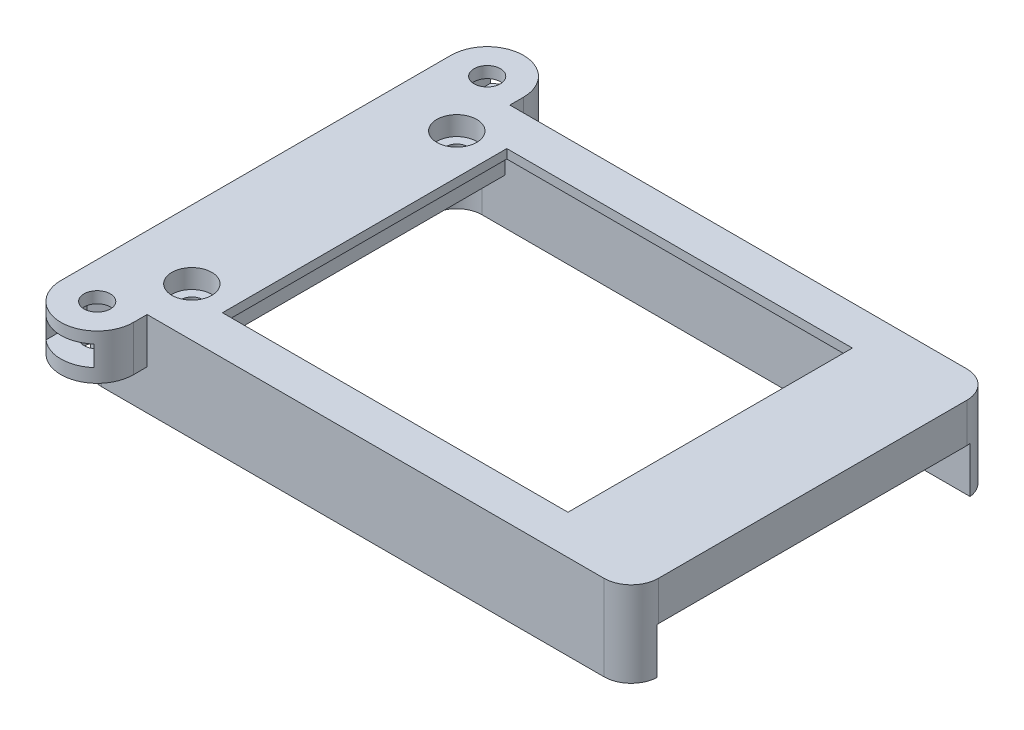
SolidWorks part; units mm, degrees
ref_plane "Front Plane" through (0, 0, 0) normal (0, 0, 1) x (1, 0, 0)
ref_plane "Top Plane" through (0, 0, 0) normal (0, 1, 0) x (1, 0, 0)
ref_plane "Right Plane" through (0, 0, 0) normal (1, 0, 0) x (0, 0, -1)
sketch "Sketch1" plane through (0, 0, 0) normal (0, 0, 1) x (1, 0, 0)
  line L0 (-23.495, -2.8321) -> (-20.447, -2.8321) construction
  line L1 (-20.447, 0) -> (-20.447, -2.8321) construction
  line L2 (-23.495, -2.8321) -> (-26.035, -2.8321) construction
  line L3 (-26.035, -2.8321) -> (-26.035, -4.4196) construction
  line L4 (-23.495, -2.8321) -> (-20.447, -2.8321) construction
  line L5 (-20.447, 0) -> (-20.447, -2.8321) construction
  line L6 (-23.495, -2.8321) -> (-26.035, -2.8321) construction
  line L7 (-26.035, -2.8321) -> (-26.035, -4.4196) construction
  line L8 (-9.4742, -6.2992) -> (-26.035, -6.2992) construction
  line L9 (-26.035, -6.2992) -> (-26.035, -4.4196) construction
  line L10 (-9.4742, -6.2992) -> (-26.035, -6.2992) construction
  line L11 (-26.035, -6.2992) -> (-26.035, -4.4196) construction
  line L12 (-20.947, 1.5) -> (-20.947, -2.8321)
  line L13 (-20.947, -2.8321) -> (-26.035, -2.8321)
  line L14 (-26.035, -2.8321) -> (-26.035, -7.9085)
  line L15 (-28.6272, -8.4085) -> (-21.9464, -8.4085) construction
  line L16 (-28.6272, -8.4085) -> (-21.9464, -8.4085) construction
  line L17 (-26.035, -7.9085) -> (-31.035, -7.9085)
  line L18 (-31.035, -7.9085) -> (-31.035, 1.5)
  line L19 (-31.035, 1.5) -> (-20.947, 1.5)
  line L20 (-20.447, 0) -> (26.0604, 0) construction
  line L21 (-20.447, 0) -> (26.0604, 0) construction
  point P14 (-29.7744, 1.574)
  dimension "D1" = 1
  dimension "D2" = 0.5
  dimension "D3" = 1.5
  dimension "D4" = 5
extrude "Boss-Extrude1" add sketch "Sketch1" along normal mid plane 40
sketch "Sketch2" plane through (0, 1.5, 0) normal (0, 1, 0) x (1, 0, 0)
  line L0 (-24.6493, -17.145) -> (-20.947, -17.145)
  line L1 (-20.947, -20) -> (-20.947, 20) construction
  line L2 (-20.947, -17.145) -> (-20.947, -20)
  line L3 (-20.947, -20) -> (-26.035, -20)
  line L4 (-20.947, -20) -> (-31.035, -20) construction
  line L5 (-26.035, -20) -> (-26.035, -17.145)
  line L6 (-26.035, -20) -> (-26.035, 20) construction
  line L7 (-26.035, -17.145) -> (-26.035, -15.7593)
  line L8 (-23.495, 17.395) -> (-23.495, 20)
  line L9 (-20.947, 20) -> (-31.035, 20) construction
  line L10 (-23.495, 20) -> (-26.035, 20)
  line L11 (-26.035, 20) -> (-26.035, 15.7593)
  arc A0 (-26.035, -14.605) -> (-23.495, -17.145) centre (-23.495, -14.605) ccw construction
  arc A1 (-26.035, -14.605) -> (-23.495, -17.145) centre (-23.495, -14.605) ccw construction
  arc A2 (-23.495, 17.145) -> (-26.035, 14.605) centre (-23.495, 14.605) ccw construction
  arc A3 (-23.495, 17.145) -> (-26.035, 14.605) centre (-23.495, 14.605) ccw construction
  arc A4 (-26.035, -15.7593) -> (-24.6493, -17.145) centre (-23.495, -14.605) ccw
  arc A5 (-26.285, -14.605) -> (-23.495, -17.395) centre (-23.495, -14.605) ccw construction
  arc A6 (-23.495, 17.395) -> (-26.035, 15.7593) centre (-23.495, 14.605) ccw
  arc A7 (-23.495, 17.395) -> (-26.285, 14.605) centre (-23.495, 14.605) ccw construction
  point P27 (-26.035, 13.7261)
  dimension "D1" = 0.25
  dimension "D2" = 0.25
extrude "Boss-Extrude2" add sketch "Sketch2" against normal up to surface (9.4085 mm away) up to face at (-28.535, -7.9085, 0)
fillet "Fillet1" radius 3 2 edges at (-31.035, -3.2043, -20) (-31.035, -3.2043, 20)
sketch "Sketch5" plane through (0, 1.5, 0) normal (0, 1, 0) x (1, 0, 0)
  line L0 (-20.947, 20) -> (27.345, 20)
  line L1 (-20.947, -20) -> (27.345, -20)
  line L2 (30.345, -17) -> (30.345, 17)
  line L3 (-20.947, -20) -> (-20.947, 20) construction
  line L4 (-20.947, -20) -> (-20.947, 20)
  line L5 (29.845, -14.605) -> (29.845, 14.605) construction
  line L8 (19.05, 15.6781) -> (19.05, -15.6781) construction
  line L9 (19.05, -15.6781) -> (-19.05, -15.6781) construction
  line L10 (19.05, 15.6781) -> (-19.05, 15.6781) construction
  line L11 (-19.05, 15.6781) -> (-19.05, -15.6781) construction
  line L12 (19.05, 15.6781) -> (19.05, -15.6781)
  line L13 (19.05, -15.6781) -> (-19.05, -15.6781)
  line L14 (19.05, 15.6781) -> (-19.05, 15.6781)
  line L15 (-19.05, 15.6781) -> (-19.05, -15.6781)
  arc A0 (27.345, -20) -> (30.345, -17) centre (27.345, -17) ccw
  arc A1 (30.345, 17) -> (27.345, 20) centre (27.345, 17) ccw
  arc A2 (-31.035, -17) -> (-28.035, -20) centre (-28.035, -17) ccw construction
  dimension "D1" = 0.5
extrude "Boss-Extrude5" add sketch "Sketch5" against normal offset from surface (1 mm away) 0.5
sketch "Sketch6" plane through (0, 0.5, 0) normal (0, -1, 0) x (1, 0, 0)
  line L0 (-23.495, 17.145) -> (27.305, 17.145) construction
  line L1 (-20.947, 17.145) -> (26.1854, 17.145)
  line L2 (26.0604, -17.145) -> (-20.447, -17.145) construction
  line L3 (-20.947, 20) -> (-20.947, -20) construction
  line L4 (-20.947, 20) -> (-20.947, 17.145)
  line L5 (27.345, 20) -> (-20.947, 20) construction
  line L6 (27.345, 20) -> (-20.947, 20)
  line L7 (-20.947, -20) -> (27.345, -20) construction
  line L8 (30.345, -17) -> (30.345, 17) construction
  line L9 (-20.947, -20) -> (27.345, -20)
  line L10 (30.345, -17) -> (30.345, 17)
  line L11 (26.0604, 17.145) -> (26.0604, 14.4018) construction
  line L12 (26.0604, 17.145) -> (26.0604, 14.4018) construction
  line L13 (26.1854, 17.145) -> (26.1854, -17.395)
  line L14 (26.0604, -17.145) -> (-20.447, -17.145) construction
  line L15 (-20.947, -20) -> (-20.947, -17.395)
  line L16 (-20.947, -17.395) -> (26.1854, -17.395)
  arc A4 (30.345, 17) -> (27.345, 20) centre (27.345, 17) ccw construction
  arc A5 (30.345, 17) -> (27.345, 20) centre (27.345, 17) ccw
  arc A6 (27.345, -20) -> (30.345, -17) centre (27.345, -17) ccw construction
  arc A7 (27.345, -20) -> (30.345, -17) centre (27.345, -17) ccw
  dimension "D2" = 0.25
  dimension "D1" = 0.25
extrude "Boss-Extrude6" add sketch "Sketch6" along normal up to surface (3.3321 mm away)
sketch "Sketch7" plane through (0, -2.8321, 0) normal (0, -1, 0) x (1, 0, 0)
  line L1 (-20.947, 20) -> (27.345, 20)
  line L2 (-20.947, 20) -> (-20.947, 17.145)
  line L3 (-20.947, 17.145) -> (30.3415, 17.145)
  line L6 (-23.495, -20) -> (27.345, -20)
  line L7 (-23.495, -20) -> (-23.495, -17.395)
  line L8 (-23.495, -17.395) -> (30.3189, -17.395)
  arc A0 (30.345, 17) -> (27.345, 20) centre (27.345, 17) ccw construction
  arc A1 (27.345, -20) -> (30.345, -17) centre (27.345, -17) ccw construction
  arc A2 (30.3415, 17.145) -> (27.345, 20) centre (27.345, 17) ccw
  arc A3 (27.345, -20) -> (30.3189, -17.395) centre (27.345, -17) ccw
  point P12 (0, 0)
extrude "Boss-Extrude7" add sketch "Sketch7" along normal up to surface (5.0764 mm away) up to face at (-25.9411, -7.9085, 1.5134)
sketch "Sketch9" plane through (0, 1.5, 0) normal (0, 1, 0) x (1, 0, 0)
  line L0 (-31.035, 17) -> (-31.035, 21.5)
  line L1 (-23.035, 21.5) -> (-23.035, 20)
  line L2 (27.345, 20) -> (-28.035, 20) construction
  line L3 (-23.035, 20) -> (-28.035, 20)
  line L4 (0, 0) -> (-7.0217, 0) construction
  line L5 (-23.035, -20) -> (-28.035, -20)
  line L6 (-23.035, -21.5) -> (-23.035, -20)
  line L7 (-31.035, -17) -> (-31.035, -21.5)
  arc A0 (-31.035, 21.5) -> (-23.035, 21.5) centre (-27.035, 21.5) cw
  arc A1 (-28.035, 20) -> (-31.035, 17) centre (-28.035, 17) ccw
  arc A2 (-28.035, -20) -> (-31.035, -17) centre (-28.035, -17) cw
  arc A3 (-31.035, -21.5) -> (-23.035, -21.5) centre (-27.035, -21.5) ccw
  dimension "D1" = 8
  dimension "D2" = 1.5
extrude "Boss-Extrude8" add sketch "Sketch9" against normal blind 5
hole_wizard "M2.5 Clearance Hole1" positions "Sketch10" profile "Sketch11" hole size "M2.5" standard "ANSI Metric" end condition through all
sketch "Sketch10" plane through (0, 1.5, 0) normal (0, 1, 0) x (1, 0, 0)
  point P0 (-27.035, -21.5)
  point P3 (-27.035, 21.5)
sketch "Sketch11" plane through (-27.035, 1.5, 21.5) normal (1, 0, 0) x (0, 0, 1)
  line L0 (0, 0) -> (0, 9.4085)
  line L1 (0, 9.4085) -> (1.45, 9.4085)
  line L2 (1.45, 9.4085) -> (1.45, 0)
  line L5 (1.45, 0) -> (0, 0)
  line L11 (0, -6.35) -> (0, 107.95) construction
  dimension "Thru Hole Dia." = 2.9
  dimension "Thru Hole Depth" = 9.4085
ref_plane "Plane1" through (0, -2, 0) normal (0, 1, 0) x (1, 0, 0)
sketch "Sketch12" plane through (0, -2, 0) normal (0, 1, 0) x (1, 0, 0)
  line L0 (-29.685, -23.03) -> (-29.685, -29.56)
  line L1 (-24.385, -23.03) -> (-24.385, -19.97)
  line L2 (-24.385, -19.97) -> (-27.035, -18.44)
  line L3 (-27.035, -18.44) -> (-29.685, -19.97)
  line L4 (-29.685, -19.97) -> (-29.685, -23.03)
  line L5 (-29.685, -23.03) -> (-27.035, -24.56) construction
  line L6 (-27.035, -24.56) -> (-24.385, -23.03) construction
  line L13 (-29.685, -29.56) -> (-24.385, -29.56)
  line L14 (-24.385, -29.56) -> (-24.385, -23.03)
  line L15 (0, 0) -> (-12.2155, 0) construction
  line L16 (-29.685, 23.03) -> (-29.685, 29.56)
  line L17 (-29.685, 29.56) -> (-24.385, 29.56)
  line L18 (-24.385, 29.56) -> (-24.385, 23.03)
  line L19 (-24.385, 23.03) -> (-24.385, 19.97)
  line L20 (-24.385, 19.97) -> (-27.035, 18.44)
  line L21 (-27.035, 18.44) -> (-29.685, 19.97)
  line L22 (-29.685, 19.97) -> (-29.685, 23.03)
  circle A0 centre (-27.035, -21.5) radius 2.65 construction
  circle A2 centre (-27.035, -21.5) radius 2.5 construction
  dimension "D1" = 5
  dimension "D2" = 0.15
  dimension "D3" = 5
extrude "Cut-Extrude1" cut sketch "Sketch12" along normal blind 2.25
sketch "Sketch13" plane through (0, 1.5, 0) normal (0, 1, 0) x (1, 0, 0)
  circle A0 centre (-23.495, 14.605) radius 1.016 construction
  circle A1 centre (-23.495, -14.605) radius 1.016 construction
  circle A2 centre (27.305, -14.605) radius 1.016 construction
  circle A3 centre (27.305, 14.605) radius 1.016 construction
  circle A4 centre (-23.495, 14.605) radius 1.016
  circle A5 centre (-23.495, -14.605) radius 1.016
  circle A6 centre (27.305, -14.605) radius 1.016
  circle A7 centre (27.305, 14.605) radius 1.016
hole_wizard "CBORE for M2 SHCS1" positions "Sketch14" profile "Sketch15" counterbore size "M2" standard "ANSI Metric" end condition through all
sketch "Sketch14" plane through (0, 1.5, 0) normal (0, 1, 0) x (1, 0, 0)
  point P0 (-23.495, -14.605)
  point P3 (-23.495, 14.605)
sketch "Sketch15" plane through (-23.495, 1.5, 14.605) normal (1, 0, 0) x (0, 0, 1)
  line L0 (0, 0) -> (0, 9.4085)
  line L1 (0, 9.4085) -> (1.2, 9.4085)
  line L3 (1.2, 9.4085) -> (1.2, 2.1)
  line L4 (1.2, 2.1) -> (2.2, 2.1)
  line L5 (2.2, 2.1) -> (2.2, 0)
  line L7 (2.2, 0) -> (0, 0)
  line L11 (0, -6.35) -> (0, 107.95) construction
  dimension "Thru Hole Dia." = 2.4
  dimension "Thru Hole Depth" = 9.4085
  dimension "C'Bore Dia." = 4.4
  dimension "C'Bore Depth" = 2.1
